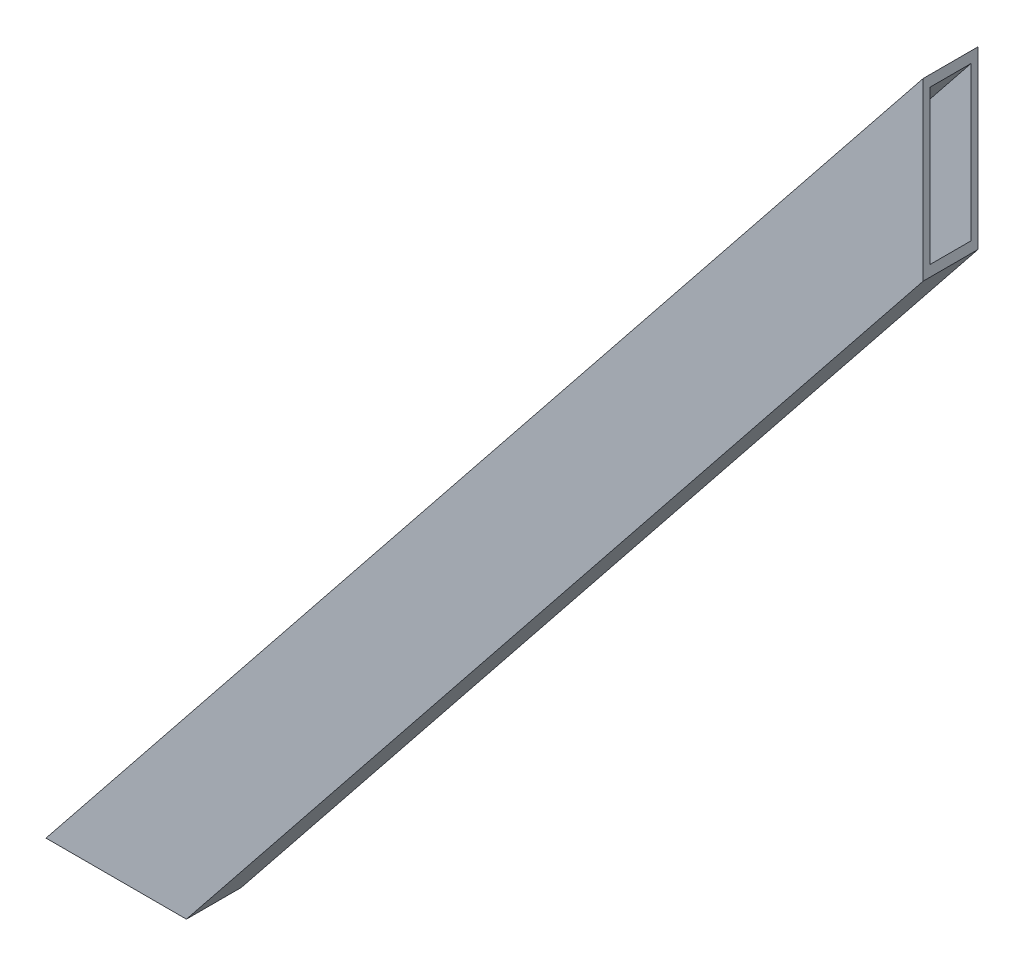
SolidWorks part; units mm, degrees
material "6063-T1"
ref_plane "Front Plane" through (0, 0, 0) normal (0, 0, 1) x (1, 0, 0)
ref_plane "Top Plane" through (0, 0, 0) normal (0, 1, 0) x (1, 0, 0)
ref_plane "Right Plane" through (0, 0, 0) normal (1, 0, 0) x (0, 0, -1)
sketch "Sketch1" plane through (0, 0, 0) normal (0, 0, 1) x (1, 0, 0)
  line L0 (0, 0) -> (406.4, 508)
  line L1 (406.4, 508) -> (406.4, 426.6803)
  line L2 (406.4, 426.6803) -> (65.0557, 0)
  line L3 (65.0557, 0) -> (0, 0)
  dimension "D1" = 406.4
  dimension "D2" = 508
  dimension "D3" = 50.8
extrude "Boss-Extrude1" add sketch "Sketch1" along normal blind 25.4
shell "Shell1" thickness 3.175 removed face at (406.4, 467.3402, 12.7) removed face at (32.5279, 0, 12.7)
